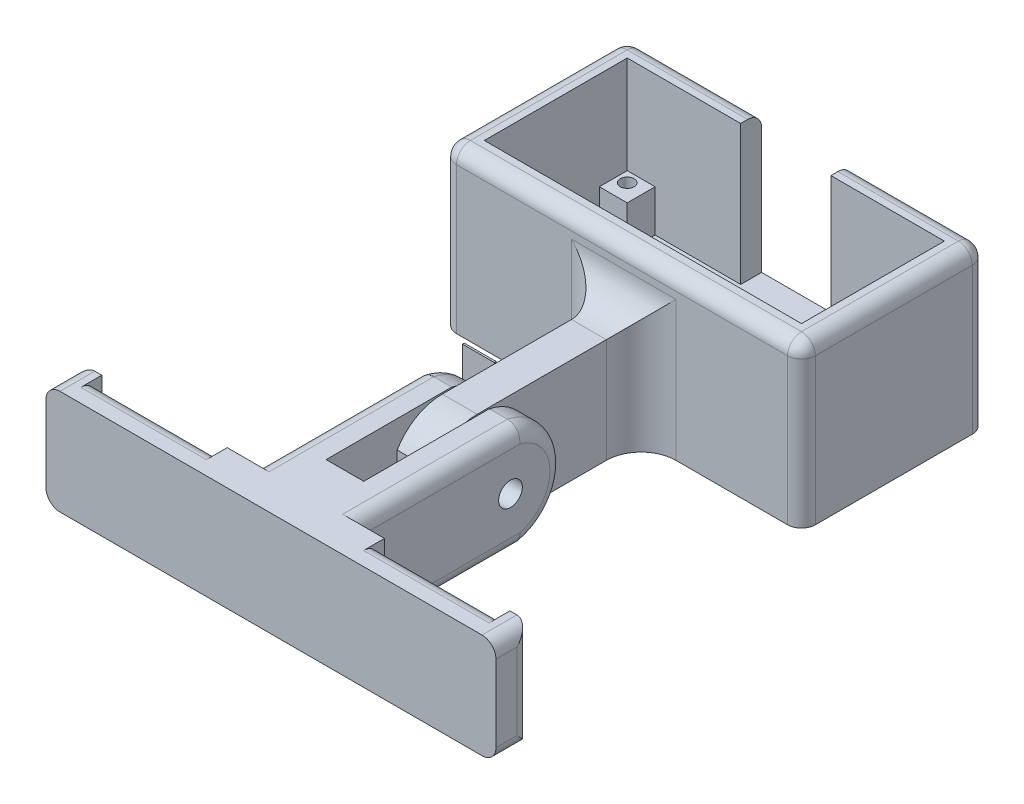
SolidWorks part; units mm, degrees
ref_plane "Спереди" through (0, 0, 0) normal (0, 0, 1) x (1, 0, 0)
ref_plane "Сверху" through (0, 0, 0) normal (0, 1, 0) x (1, 0, 0)
ref_plane "Справа" through (0, 0, 0) normal (1, 0, 0) x (0, 0, -1)
sketch "Эскиз1" plane through (0, 0, 0) normal (0, 1, 0) x (1, 0, 0)
  line L0 (-23, 0.25) -> (15.1596, 0.25) construction
  line L1 (-23, 10.5) -> (22.5, 10.5)
  line L2 (-23, 10.5) -> (-23, -10)
  line L3 (-23, -10) -> (22.5, -10)
  line L4 (22.5, 10.5) -> (22.5, -10)
  line L5 (18.5, -6) -> (22.5, -6)
  line L6 (18.5, 10.5) -> (18.5, 6.5)
  line L7 (18.5, -10) -> (18.5, -6)
  line L8 (-0.25, 0) -> (-0.25, 7.045) construction
  line L9 (-0.25, 10.5) -> (-0.25, 0) construction
  line L10 (22.5, 10.5) -> (20.212, 8.3843) construction
  line L11 (-19, -10) -> (-19, -6)
  line L12 (-19, 10.5) -> (-23, 10.5)
  line L13 (6.2185, 10.5) -> (6.2185, 20.0274)
  line L14 (6.2185, 20.0274) -> (-6.7185, 20.0274)
  line L15 (-6.7185, 10.5) -> (-6.7185, 20.0274)
  line L16 (-0.25, 10.5) -> (-6.7185, 20.0274) construction
  line L17 (6.2185, 20.0274) -> (-0.25, 10.5) construction
  line L18 (-19, 10.5) -> (-19, 6.5)
  line L19 (-19, 6.5) -> (-23, 6.5)
  line L20 (-23, 10.5) -> (-23, 6.5)
  line L21 (-19, -6) -> (-23, -6)
  line L23 (18.5, 6.5) -> (22.5, 6.5)
  line L24 (-26, 13.5) -> (25.5, 13.5)
  line L25 (-26, 13.5) -> (-26, -13)
  line L26 (-26, -13) -> (25.5, -13)
  line L27 (25.5, 13.5) -> (25.5, -13)
  line L28 (-26, 13.5) -> (25.5, -13) construction
  line L29 (-26, -13) -> (25.5, 13.5) construction
  circle A0 centre (-21.5, 9) radius 1
  circle A1 centre (21, 9) radius 1
  circle A2 centre (21, -8.5) radius 1
  circle A3 centre (-21.5, -8.5) radius 1
  point P0 (0, 0)
  point P41 (-0.25, 0.25)
  dimension "D3" = 1.5
  dimension "D4" = 4
  dimension "D1" = 45.5
  dimension "D2" = 20.5
  dimension "D5" = 4
  dimension "D6" = 3
  dimension "D7" = 3
  dimension "D8" = 3
  dimension "D9" = 3
  dimension "D10" = 1.5
  dimension "D11" = 1.5
  dimension "D12" = 1.5
  dimension "D13" = 1.5
  dimension "D14" = 1.5
extrude "Бобышка-Вытянуть1" add sketch "Эскиз1" along normal blind 20 contours L27 L24 L13 L1 L4 L3 L2 L15 L25 L26 region at (-23.5792, 0, -8.5)
extrude "Бобышка-Вытянуть2" add sketch "Эскиз1<3>" along normal blind 6 contours L19 L18 L1 L2 A0 | L6 L23 L4 L1 A1 | L7 L3 L4 L5 A2 | L11 L21 L2 L3 A3 region at (-21, 0, -10.4434) region at (-21, 0, 6.0566) region at (20.5, 0, -10.4434) region at (18.5566, 0, 8)
sketch "Эскиз1<3>" plane through (0, 0, 0) normal (0, 1, 0) x (1, 0, 0) same geometry as "Эскиз1"
extrude "Бобышка-Вытянуть3" add sketch "Эскиз1<4>" against normal blind 3 contours L27 L24 L13 L1 L4 L3 L2 L15 L25 L26 | L23 L6 L1 L18 L19 L2 L21 L11 L3 L7 L5 L4 | L7 L3 L4 L5 A2 | L6 L23 L4 L1 A1 | A3 | L11 L21 L2 L3 A3 | L19 L18 L1 L2 A0 | A0 | A1 | A2 | L24 L15 L1 L13 region at (-23.5792, 0, -8.5) region at (-21, 0, -10.4434) region at (-0.25, 0, -0.25) region at (-0.25, 0, -12) region at (-21, 0, 6.0566) region at (20.5, 0, -10.4434) region at (18.5566, 0, 8) region at (-21.5, 0, -9) region at (21, 0, -9) region at (21, 0, 8.5) region at (-21.5, 0, 8.5)
sketch "Эскиз1<4>" plane through (0, 0, 0) normal (0, 1, 0) x (1, 0, 0) same geometry as "Эскиз1"
fillet "Скругление1" radius 2 9 edges at (-26, 20, -0.25) (-16.3593, 20, -13.5) (15.8593, 20, -13.5) (25.5, 20, -0.25) (-0.25, 20, 13) (-26, 8.5, 13) (-26, 8.5, -13.5) (25.5, 8.5, -13.5) (25.5, 8.5, 13)
sketch "Эскиз3" plane through (0, -3, 0) normal (0, -1, 0) x (1, 0, 0)
  line L0 (0, 0) -> (0, 43.8421) construction
  line L1 (-24, 13) -> (23.5, 13) construction
  line L2 (2.5, 43) -> (-2.5, 43)
  line L3 (0, 43) -> (0, 43.8421)
  line L4 (2.5, 13) -> (-2.5, 13)
  line L5 (-2.5, 43) -> (-2.5, 13)
  line L6 (0, 43) -> (-2.5, 13) construction
  line L7 (0, 13) -> (-2.5, 43) construction
  line L8 (2.5, 43) -> (2.5, 13)
  point P7 (-1.25, 28)
  line M5 (23.5, 13) -> (-24, 13)
  dimension "D1" = 30
  dimension "D2" = 2.5
extrude "Бобышка-Вытянуть4" add sketch "Эскиз3" against normal blind 15 contours L8 L2 L5 M5 region at (0, -3, 28)
sketch "Эскиз4" plane through (-2.5, 0, 0) normal (-1, 0, 0) x (0, 0, 1)
  line L0 (43, 4.5) -> (18.2521, 4.5) construction
  line L1 (43, 12) -> (43, -3) construction
  line L2 (36.5255, 12) -> (43, 12)
  line L3 (43, 12) -> (43, -3)
  line L4 (43, -3) -> (36.5255, -3)
  arc A0 (36.5255, -3) -> (36.5255, 12) centre (36.5255, 4.5) ccw
  circle A1 centre (36.5255, 4.5) radius 1.8
  line M1 (13, -3) -> (43, -3)
  line M2 (43, -3) -> (43, 12)
  line M3 (43, 12) -> (13, 12)
extrude "Вырез-Вытянуть1" cut sketch "Эскиз4" against normal blind 5 contours A0 M2 M3 | A0 M1 M2 | A1 L0 | L0 A1 region at (-2.5, 3.7361, 36.5255) region at (-2.5, 5.2639, 36.5255) region at (-2.5, 10.9567, 41.4722) region at (-2.5, -1.9567, 41.4722)
fillet "Скругление2" radius 5 3 edges at (0, 12, 13) (2.5, 4.5, 13) (-2.5, 4.5, 13)
sketch "Эскиз5" plane through (0, -3, 0) normal (0, -1, 0) x (1, 0, 0)
  line L0 (0, 43) -> (0, 64.1698) construction
  line L1 (2.5, 43) -> (-2.5, 43) construction
  line L2 (2.7, 53) -> (-2.7, 53)
  line L3 (-2.7, 53) -> (-2.7, 28.6069)
  line L4 (-2.7, 28.6069) -> (-7.2775, 28.6069)
  line L5 (-7.2775, 28.6069) -> (-7.2775, 58.6069)
  line L6 (-7.2775, 58.6069) -> (-11.2775, 58.6069)
  line L7 (-32.2775, 58.6069) -> (-32.2775, 63.6069)
  line L8 (-32.2775, 63.6069) -> (32.2775, 63.6069)
  line L9 (-29.2775, 59.6069) -> (-11.2775, 59.6069)
  line L10 (-2.5, 36.5255) -> (-2.5, 18) construction
  line L11 (2.7, 53) -> (2.7, 28.8677)
  line L12 (2.7, 28.8677) -> (7.2775, 28.8677)
  line L13 (7.2775, 28.8677) -> (7.2775, 58.6069)
  line L14 (32.2775, 58.6069) -> (32.2775, 63.6069)
  line L15 (7.2775, 58.6069) -> (11.2775, 58.6069)
  line L16 (-29.2775, 59.6069) -> (-29.2775, 58.6069)
  line L17 (11.2775, 59.6069) -> (11.2775, 58.6069)
  line L18 (-11.2775, 59.6069) -> (-11.2775, 58.6069)
  line L19 (-29.2775, 58.6069) -> (-32.2775, 58.6069)
  line L20 (29.2775, 59.6069) -> (11.2775, 59.6069)
  line L21 (29.2775, 59.6069) -> (29.2775, 58.6069)
  line L22 (29.2775, 58.6069) -> (32.2775, 58.6069)
  dimension "D1" = 0.2
  dimension "D2" = 10
  dimension "D3" = 30
  dimension "D4" = 25
  dimension "D5" = 5
  dimension "D6" = 1
  dimension "D7" = 3
  dimension "D8" = 18
extrude "Бобышка-Вытянуть5" add sketch "Эскиз5" against normal blind 15 separate body
sketch "Эскиз6" plane through (7.2775, 0, 0) normal (1, 0, 0) x (0, 0, -1)
  line L0 (-28.8677, 4.5) -> (-46.2458, 4.5) construction
  line L1 (-28.8677, 12) -> (-28.8677, -3) construction
  line L2 (-28.8677, 12) -> (-28.8677, -3)
  line L3 (-28.8677, -3) -> (-36.5255, -3.1578)
  line L4 (-28.8677, 12) -> (-36.5255, 12.1578)
  circle A0 centre (-36.5255, 4.5) radius 1.7
  arc A1 (-36.5255, -3.1578) -> (-36.5255, 12.1578) centre (-36.5255, 4.5) ccw
  line M1 (-58.6069, -3) -> (-28.8677, -3)
  line M2 (-28.8677, -3) -> (-28.8677, 12)
  line M3 (-28.8677, 12) -> (-58.6069, 12)
extrude "Вырез-Вытянуть2" cut sketch "Эскиз6" against normal blind 15 contours A1 L2 M3 | A1 M1 M2 | A0 L0 | L0 A0 region at (7.2775, 3.7785, 36.5255) region at (7.2775, 5.2215, 36.5255) region at (7.2775, 10.2993, 30.4322) region at (7.2775, -1.2993, 30.4322)
fillet "Скругление3" radius 2 16 edges at (32.2775, 12, 61.1069) (-32.2775, 12, 61.1069) (-32.2775, -3, 61.1069) (32.2775, -3, 61.1069) (20.2775, -3, 59.6069) (20.2775, 12, 59.6069) (-20.2775, 12, 59.6069) (-20.2775, -3, 59.6069) (-32.2775, 4.5, 58.6069) (32.2775, 4.5, 58.6069) (-7.2775, 4.5, 28.8677) (7.2775, 4.5, 28.8677) (-7.2775, -3, 46.7928) (7.2775, -3, 46.7928) (-7.2775, 12, 46.7928) (7.2775, 12, 46.7928)
